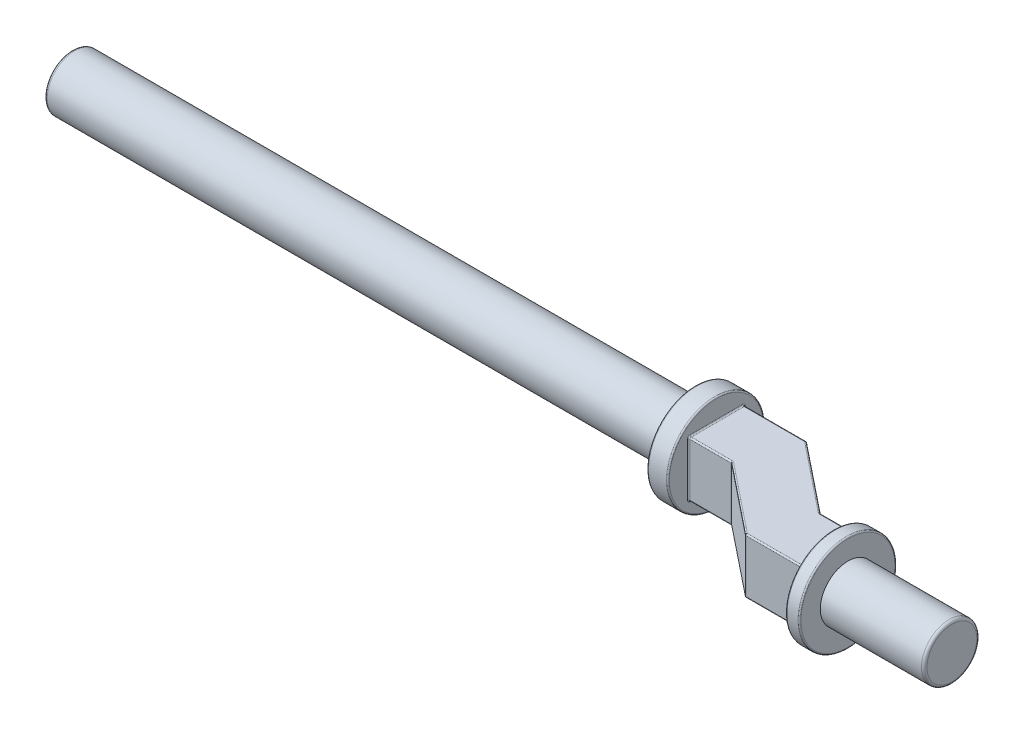
SolidWorks part; units mm, degrees
ref_plane "前视基准面" through (0, 0, 0) normal (0, 0, 1) x (1, 0, 0)
ref_plane "上视基准面" through (0, 0, 0) normal (0, 1, 0) x (1, 0, 0)
ref_plane "右视基准面" through (0, 0, 0) normal (1, 0, 0) x (0, 0, -1)
sketch "草图1" plane through (0, 0, 0) normal (1, 0, 0) x (0, 0, -1)
  circle A0 centre (0, 0) radius 2
  dimension "D1" = 4
extrude "凸台-拉伸1" add sketch "草图1" along normal blind 45
sketch "草图2" plane through (45, 0, 0) normal (1, 0, 0) x (0, 0, -1)
  circle A0 centre (0, 0) radius 3.5
  dimension "D1" = 7
extrude "凸台-拉伸2" add sketch "草图2" along normal blind 1.5
sketch "草图3" plane through (0, 0, 0) normal (0, 1, 0) x (1, 0, 0)
  line L0 (46.5, 0) -> (46.5, 2) construction
  line L1 (46.5, -3.5) -> (46.5, 3.5) construction
  line L2 (46.5, 2) -> (51, 2)
  line L3 (51, 2) -> (56, -2)
  line L4 (56, -2) -> (59, -2)
  line L5 (46.5, -2) -> (49.5969, -2)
  line L6 (49.5969, -2) -> (54.5969, -6)
  line L7 (54.5969, -6) -> (59, -6)
  line L8 (46.5, 2) -> (46.5, -2)
  line L9 (59, -2) -> (59, -6)
  dimension "D1" = 4.5
  dimension "D2" = 2
  dimension "D3" = 3
  dimension "D4" = 12.5
  dimension "D5" = 4
  dimension "D6" = 4
extrude "凸台-拉伸3" add sketch "草图3" along normal blind 2 and the other way blind 2
sketch "草图4" plane through (59, 0, 0) normal (1, 0, 0) x (0, 0, -1)
  line L0 (-6, 0) -> (-4, 0) construction
  line L1 (-6, -2) -> (-6, 2) construction
  circle A0 centre (-4, 0) radius 3.5
  dimension "D2" = 7
  dimension "D1" = 2
extrude "凸台-拉伸4" add sketch "草图4" along normal blind 1
sketch "草图5" plane through (60, 0, 0) normal (1, 0, 0) x (0, 0, -1)
  circle A0 centre (-4, 0) radius 2
  dimension "D1" = 4
extrude "凸台-拉伸5" add sketch "草图5" along normal blind 7.5
fillet "圆角1" radius 0.2 2 edges at (0, 0, -2) (67.5, 0, 2)
fillet "圆角2" radius 0.1 28 edges at (54.5969, 0, 6) (59, 0, 6) (46.5, 0, 2) (49.5969, 0, 2) (59, 0, 2) (56, 0, 2) (51, 0, -2) (46.5, 0, -2) (48.0484, -2, 2) (52.0969, -2, 4) (56.7984, -2, 6) (59, -2, 4) (57.5, -2, 2) (53.5, -2, 0) (48.75, -2, -2) (46.5, -2, 0) (48.75, 2, -2) (53.5, 2, 0) (57.5, 2, 2) (59, 2, 4) (56.7984, 2, 6) (52.0969, 2, 4) (48.0484, 2, 2) (46.5, 2, 0) (59, 0, 0.5) (60, 0, 0.5) (45, 0, -3.5) (46.5, 0, -3.5)
